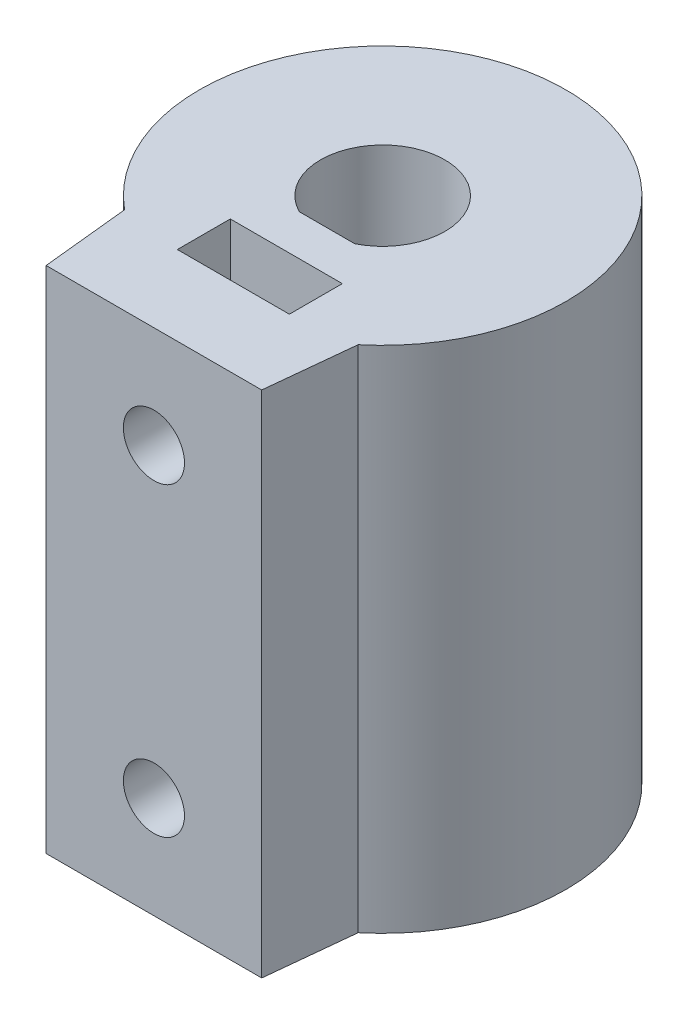
SolidWorks part; units mm, degrees
material "ABS"
ref_plane "Спереди" through (0, 0, 0) normal (0, 0, 1) x (1, 0, 0)
ref_plane "Сверху" through (0, 0, 0) normal (0, 1, 0) x (1, 0, 0)
ref_plane "Справа" through (0, 0, 0) normal (1, 0, 0) x (0, 0, -1)
sketch "Эскиз1" plane through (0, 0, 0) normal (0, 1, 0) x (1, 0, 0)
  circle A0 centre (0, 0) radius 6
  circle A1 centre (0, 0) radius 3.05
  dimension "D1" = 6.1
  dimension "D2" = 12
extrude "Бобышка-Вытянуть1" add sketch "Эскиз1" along normal blind 25
sketch "Эскиз2" plane through (0, 0, 0) normal (0, -1, 0) x (1, 0, 0)
  line L1 (-2.329, 4.73) -> (2.376, 4.73)
  line L2 (-2.329, 4.73) -> (-2.329, 2.73)
  line L3 (-2.329, 2.73) -> (2.376, 2.73)
  line L4 (2.376, 4.73) -> (2.376, 2.73)
  dimension "D1" = 2
  dimension "D2" = 2.73
extrude "Бобышка-Вытянуть2" add sketch "Эскиз2" against normal blind 12
sketch "Эскиз4" plane through (0, 0, 0) normal (0, -1, 0) x (1, 0, 0)
  line L0 (-1.36, 2.73) -> (1.36, 2.73) construction
  line L1 (-5.25, 2.73) -> (5.25, 2.73)
  line L2 (-5.25, 2.73) -> (-5.25, 9.23)
  line L3 (-5.25, 9.23) -> (5.25, 9.23)
  line L4 (5.25, 2.73) -> (5.25, 9.23)
  point P6 (0, 2.73)
  point P7 (0, 9.23)
  dimension "D1" = 6.5
  dimension "D4" = 10.5
extrude "Бобышка-Вытянуть3" add sketch "Эскиз4" against normal through all
sketch "Эскиз5" plane through (0, 0, 0) normal (0, -1, 0) x (1, 0, 0)
  line L1 (-1.36, 2.73) -> (1.36, 2.73) construction
  line L2 (-2.75, 7.33) -> (2.75, 7.33)
  line L3 (-2.75, 7.33) -> (-2.75, 4.73)
  line L4 (-2.75, 4.73) -> (2.75, 4.73)
  line L5 (2.75, 7.33) -> (2.75, 4.73)
  line L6 (5.25, 9.23) -> (-5.25, 9.23) construction
  point P5 (0, 7.33)
  dimension "D1" = 2
  dimension "D2" = 2.6
  dimension "D3" = 5.5
  dimension "D4" = 1.9
fillet "Скругление1" [suppressed] radius 1
sketch "Эскиз6" plane through (0, 0, 9.23) normal (0, 0, 1) x (1, 0, 0)
  line L0 (5.25, 0) -> (-5.25, 0) construction
  circle A0 centre (0, 5) radius 1.5
  dimension "D1" = 3
  dimension "D2" = 5
extrude "Вырез-Вытянуть3" cut sketch "Эскиз6" against normal blind 10
extrude "Вырез-Вытянуть4" cut sketch "Эскиз5" against normal blind 5
sketch "Эскиз11" plane through (0, 0, 7.33) normal (0, 0, -1) x (-1, 0, 0)
  line L2 (-2.75, 6.5877) -> (-2.75, 7.0877)
  line L3 (0, 1.8246) -> (2.75, 3.4123)
  line L4 (2.75, 3.4123) -> (2.75, 6.5877)
  line L7 (-2.75, 6.5877) -> (-2.75, 3.4123)
  line L8 (-2.75, 3.4123) -> (0, 1.8246)
  line L9 (-2.75, 7.0877) -> (0, 8.6754)
  line L10 (0, 8.6754) -> (2.75, 7.0877)
  line L11 (2.75, 7.0877) -> (2.75, 6.5877)
  line L14 (2.75, 6.5877) -> (1.375, 7.3816) [skipped]
  line L15 (-1.375, 7.3816) -> (-2.75, 6.5877) [skipped]
  circle A0 centre (0, 5) radius 2.75 construction
  dimension "D1" = 5.5
  dimension "D2" = 0.5
extrude "Вырез-Вытянуть8" cut sketch "Эскиз11" along normal up to surface (2.6 mm away) up to face at (0, 3.0833, 4.73)
ref_plane "Плоскость1" through (0, 12.5, 0) normal (0, -1, 0) x (-1, 0, 0)
mirror "Зеркальное отражение1" about plane through (0, 12.5, 0) normal (0, -1, 0) of "Вырез-Вытянуть4", "Вырез-Вытянуть8", "Вырез-Вытянуть3"
sketch "Эскиз13" plane through (0, 25, 0) normal (0, 1, 0) x (1, 0, 0)
  line L1 (-5.25, -2.9047) -> (-5.25, -9.23)
  line L2 (5.25, -2.9047) -> (5.25, -9.23)
  arc A0 (5.25, -9.23) -> (-5.25, -9.23) centre (0, 0) ccw
  arc A1 (5.25, -2.9047) -> (-5.25, -2.9047) centre (0, 0) ccw
  arc A2 (5.25, -2.9047) -> (-5.25, -2.9047) centre (0, 0) ccw construction
extrude "Бобышка-Вытянуть4" add sketch "Эскиз13" against normal through all
sketch "Эскиз14" plane through (0, 0, 9.23) normal (0, 0, 1) x (1, 0, 0)
  line L1 (-5.25, 25) -> (5.25, 25)
  line L2 (-5.25, 25) -> (-5.25, 0)
  line L3 (-5.25, 0) -> (5.25, 0)
  line L4 (5.25, 25) -> (5.25, 0)
  circle A0 centre (0, 20) radius 1.5
  circle A1 centre (0, 5) radius 1.5
extrude "Бобышка-Вытянуть5" add sketch "Эскиз14" along normal blind 2
sketch "Эскиз15" plane through (0, 0, 0) normal (0, -1, 0) x (1, 0, 0)
  line L0 (-5.25, 9.23) -> (-5.25, 7.3101)
  line L1 (5.25, 9.23) -> (5.25, 7.3101)
  arc A0 (-5.25, 7.3101) -> (5.25, 7.3101) centre (0, 0) ccw
  arc A1 (-5.25, 9.23) -> (5.25, 9.23) centre (0, 0) ccw
  dimension "D1" = 18
extrude "Вырез-Вытянуть9" cut sketch "Эскиз15" against normal through all
chamfer "Фаска1" distance 1 angle 45 1 edges at (-5.25, 12.5, 7.3101) first distance on face at (0, 12.5, -0.845)
chamfer "Фаска2" distance 1 angle 45 1 edges at (5.25, 12.5, 7.3101) first distance on face at (0.0318, 12.5, -0.9357)
